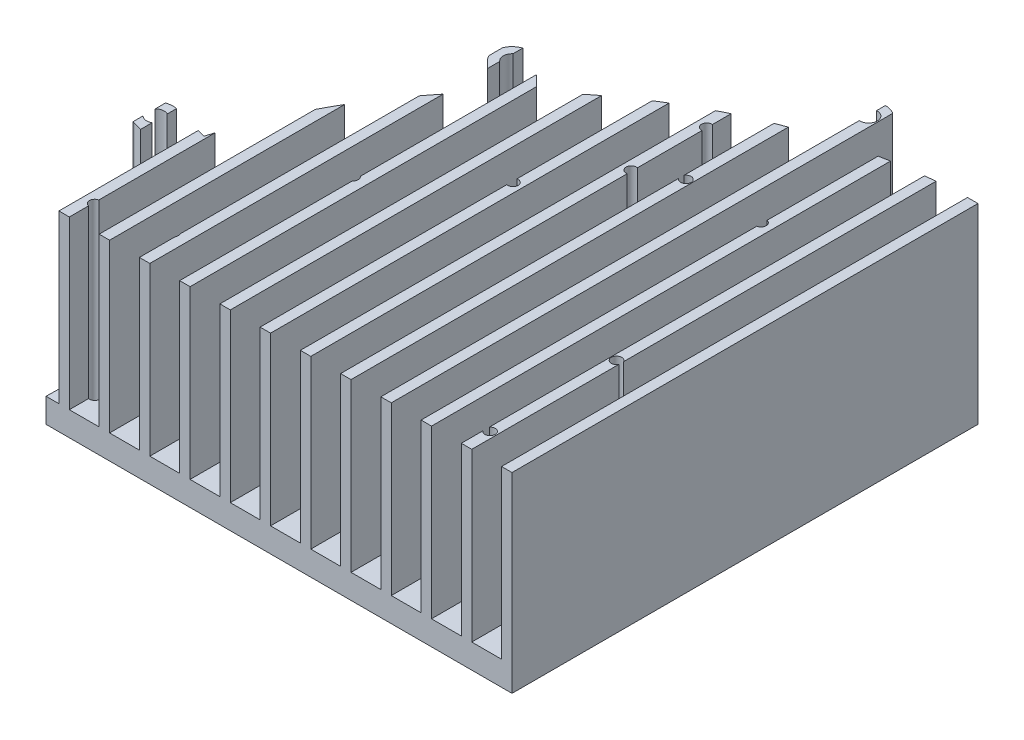
SolidWorks part; units mm, degrees
note: The reader was unsure of these and kept them because the rebuilt part matched: shared geometry of "Sketch3<6>".
ref_plane "Ön Düzlem" through (0, 0, 0) normal (0, 0, 1) x (1, 0, 0)
ref_plane "Üst Düzlem" through (0, 0, 0) normal (0, 1, 0) x (1, 0, 0)
ref_plane "Sağ Düzlem" through (0, 0, 0) normal (1, 0, 0) x (0, 0, -1)
sketch "Sketch1" plane through (0, 0, 0) normal (0, 0, 1) x (1, 0, 0)
  line L0 (11.5714, 7) -> (11.5714, 55)
  line L1 (0, 0) -> (165, 0)
  line L2 (0, 0) -> (0, 7)
  line L3 (3, 7) -> (11.5714, 7)
  line L4 (165, 0) -> (165, 10)
  line L6 (0, 7) -> (0, 55)
  line L7 (0, 55) -> (3, 55)
  line L8 (3, 7) -> (3, 55)
  line L10 (14.5714, 7) -> (14.5714, 55)
  line L11 (11.5714, 55) -> (14.5714, 55)
  line L12 (23.1429, 7) -> (23.1429, 55)
  line L14 (26.1429, 7) -> (26.1429, 55)
  line L15 (23.1429, 55) -> (26.1429, 55)
  line L16 (34.7143, 7) -> (34.7143, 55)
  line L18 (37.7143, 7) -> (37.7143, 55)
  line L19 (34.7143, 55) -> (37.7143, 55)
  line L20 (46.2857, 7) -> (46.2857, 55)
  line L22 (49.2857, 7) -> (49.2857, 55)
  line L23 (46.2857, 55) -> (49.2857, 55)
  line L24 (57.8571, 7) -> (57.8571, 55)
  line L26 (60.8571, 7) -> (60.8571, 55)
  line L27 (57.8571, 55) -> (60.8571, 55)
  line L28 (69.4286, 7) -> (69.4286, 55)
  line L30 (72.4286, 7) -> (72.4286, 55)
  line L31 (69.4286, 55) -> (72.4286, 55)
  line L32 (81, 7) -> (81, 55)
  line L34 (84, 7) -> (84, 55)
  line L35 (81, 55) -> (84, 55)
  line L36 (92.5714, 7) -> (92.5714, 55)
  line L38 (95.5714, 7) -> (95.5714, 55)
  line L39 (92.5714, 55) -> (95.5714, 55)
  line L40 (104.1429, 7) -> (104.1429, 55)
  line L42 (107.1429, 7) -> (107.1429, 55)
  line L43 (104.1429, 55) -> (107.1429, 55)
  line L44 (115.7143, 7) -> (115.7143, 55)
  line L46 (118.7143, 7) -> (118.7143, 55)
  line L47 (115.7143, 55) -> (118.7143, 55)
  line L48 (127.2857, 7) -> (127.2857, 55)
  line L50 (130.2857, 7) -> (130.2857, 55)
  line L51 (127.2857, 55) -> (130.2857, 55)
  line L52 (138.8571, 7) -> (138.8571, 55)
  line L54 (141.8571, 7) -> (141.8571, 55)
  line L55 (138.8571, 55) -> (141.8571, 55)
  line L56 (150.4286, 7) -> (150.4286, 55)
  line L58 (153.4286, 7) -> (153.4286, 55)
  line L59 (150.4286, 55) -> (153.4286, 55)
  line L60 (162, 7) -> (162, 55)
  line L62 (165, 7) -> (165, 55)
  line L63 (162, 55) -> (165, 55)
  line L78 (14.5714, 7) -> (23.1429, 7)
  line L79 (26.1429, 7) -> (34.7143, 7)
  line L80 (37.7143, 7) -> (46.2857, 7)
  line L81 (49.2857, 7) -> (57.8571, 7)
  line L82 (60.8571, 7) -> (69.4286, 7)
  line L83 (72.4286, 7) -> (81, 7)
  line L84 (84, 7) -> (92.5714, 7)
  line L85 (95.5714, 7) -> (104.1429, 7)
  line L86 (107.1429, 7) -> (115.7143, 7)
  line L87 (118.7143, 7) -> (127.2857, 7)
  line L88 (130.2857, 7) -> (138.8571, 7)
  line L89 (141.8571, 7) -> (150.4286, 7)
  line L90 (153.4286, 7) -> (162, 7)
  dimension "D1" = 165
  dimension "D2" = 7
  dimension "D3" = 48
  dimension "D4" = 3
  dimension "D5" = 15
extrude "Boss-Extrude1" add sketch "Sketch1" along normal blind 1000 contours L90 L58 L59 L56 L89 L54 L55 L52 L88 L50 L51 L48 L87 L46 L47 L44 L86 L42 L43 L40 L85 L38 L39 L36 L84 L34 L35 L32 L83 L30 L31 L28 L82 L26 L27 L24 L81 L22 L23 L20 L80 L18 L19 L16 L79 L14 L15 L12 L78 L10 L11
sketch "Sketch3" plane through (0, 0, 0) normal (0, -1, 0) x (1, 0, 0)
  line L1 (165, 1000) -> (165, 0) construction
  line L3 (0, 0) -> (165, 0) construction
  line L23 (165, 200) -> (0, 200) construction
  line L24 (0, 1000) -> (0, 0) construction
  line L25 (165, 334) -> (0, 334) construction
  line L26 (165, 334) -> (118.1105, 159.006) construction
  line L27 (165, 334) -> (36.8955, 205.8955) construction
  line L28 (165, 334) -> (-9.994, 287.1105) construction
  line L29 (165, 334) -> (118.1105, 159.006) construction
  line L30 (165, 334) -> (127.4712, 193.9408) construction
  line L31 (165, 334) -> (127.4712, 193.9408) construction
  line L32 (132.3009, 192.6467) -> (135.172, 203.362)
  line L33 (122.6416, 195.2349) -> (125.5128, 205.9502)
  line L34 (66.0051, 227.934) -> (73.8492, 235.7781)
  line L35 (58.934, 235.0051) -> (66.7781, 242.8492)
  line L36 (26.2349, 291.6416) -> (36.9502, 294.5128)
  line L37 (23.6467, 301.3009) -> (34.362, 304.172)
  line L38 (165, 334) -> (135.172, 203.362) construction
  line L39 (165, 200) -> (165, 334)
  line L40 (165, 334) -> (31, 334)
  line L41 (165, 184) -> (0, 184) construction
  line L42 (165, 344) -> (0, 344) construction
  line L43 (0, 184) -> (0, 344) construction
  line L44 (165, 200) -> (165, 184) construction
  line L45 (165, 344) -> (165, 334) construction
  arc A1 (165, 200) -> (31, 334) centre (165, 334) cw construction
  circle A7 centre (117, 236) radius 1.5
  circle A8 centre (106.834, 241.544) radius 1.5
  arc A10 (165, 184) -> (15, 334) centre (165, 334) cw construction
  arc A11 (165, 189) -> (20, 334) centre (165, 334) cw construction
  circle A12 centre (127.4712, 193.9408) radius 2.5
  circle A13 centre (62.4695, 231.4695) radius 2.5
  circle A14 centre (24.9408, 296.4712) radius 2.5
  arc A15 (122.6646, 195.3179) -> (132.3225, 192.7301) centre (127.4712, 193.9408) ccw
  arc A16 (58.9955, 235.0655) -> (66.0655, 227.9955) centre (62.4695, 231.4695) ccw
  arc A17 (23.7301, 301.3225) -> (26.3179, 291.6646) centre (24.9408, 296.4712) ccw
  arc A18 (165, 200) -> (135.172, 203.362) centre (165, 334) cw
  arc A19 (125.5128, 205.9502) -> (73.8492, 235.7781) centre (165, 334) cw
  arc A20 (66.7781, 242.8492) -> (36.9502, 294.5128) centre (165, 334) cw
  arc A21 (34.362, 304.172) -> (31, 334) centre (165, 334) cw
  circle A22 centre (159, 206) radius 1.5
  circle A23 centre (159.945, 224.958) radius 1.5
  circle A24 centre (138.59, 236) radius 1.5
  circle A25 centre (107, 220) radius 1.5
  circle A26 centre (92.864, 261.61) radius 1.5
  circle A27 centre (74.576, 273.548) radius 1.5
  circle A28 centre (68.48, 283.2) radius 1.5
  circle A29 centre (51, 276) radius 1.5
  circle A30 centre (152.097, 291.028) radius 1.5
  circle A31 centre (133.3, 304.5) radius 1.5
  circle A32 centre (66.702, 306.822) radius 1.5
  circle A33 centre (56.542, 323.078) radius 1.5
  circle A34 centre (38, 327) radius 1.5
  circle A35 centre (124, 325) radius 1.5
  circle A36 centre (158, 321) radius 1.501
  circle A37 centre (151.6, 326.9) radius 1.5
  dimension "D5" = 48
  dimension "D7" = 3
  dimension "D8" = 3
  dimension "D10" = 92.456
  dimension "D20" = 150
  dimension "D21" = 145
  dimension "D22" = 134
  dimension "D23" = 5
  dimension "D26" = 10
  dimension "D32" = 3
  dimension "D35" = 3
  dimension "D38" = 3
  dimension "D41" = 3
  dimension "D11" = 3
  dimension "D44" = 3
  dimension "D47" = 3
  dimension "D50" = 3
  dimension "D53" = 3
  dimension "D56" = 3
  dimension "D61" = 3
  dimension "D62" = 3
  dimension "D65" = 3
  dimension "D68" = 3
  dimension "D69" = 3.002
  dimension "D70" = 3
  dimension "D6" = 98
  dimension "D9" = 58.166
  dimension "D14" = 134
  dimension "D15" = 200
  dimension "D16" = 15
  dimension "D18" = 30
  dimension "D19" = 30
  dimension "D25" = 145
  dimension "D28" = 145
  dimension "D30" = 134
  dimension "D31" = 10
  dimension "D33" = 6
  dimension "D34" = 128
  dimension "D36" = 5.055
  dimension "D37" = 109.042
  dimension "D39" = 26.41
  dimension "D40" = 98
  dimension "D42" = 58
  dimension "D43" = 114
  dimension "D12" = 72.136
  dimension "D13" = 72.39
  dimension "D45" = 60.452
  dimension "D46" = 90.424
  dimension "D48" = 50.8
  dimension "D49" = 96.52
  dimension "D51" = 114
  dimension "D52" = 58
  dimension "D54" = 12.903
  dimension "D55" = 42.972
  dimension "D57" = 29.5
  dimension "D58" = 31.7
  dimension "D59" = 98.298
  dimension "D60" = 27.178
  dimension "D63" = 108.458
  dimension "D64" = 10.922
  dimension "D66" = 7
  dimension "D67" = 127
  dimension "D71" = 41
  dimension "D72" = 9
  dimension "D73" = 7
  dimension "D74" = 13
  dimension "D75" = 13.4
  dimension "D76" = 7.1
  dimension "D17" = 3
  dimension "D24" = 3
  dimension "D27" = 3
  dimension "D29" = 3
extrude "Cut-Extrude3" cut sketch "Sketch3" against normal blind 100
extrude "Cut-Extrude4" cut sketch "Sketch3<6>" against normal blind 100 contours A12 | A13 | A14 | A23 | A22 | A24 | A25 | A7 | A8 | A26 | A27 | A29 | A28 | A32 | A34 | A33 | A35 | A31 | A30 | A37 | A36
sketch "Sketch3<6>" plane through (0, 0, 0) normal (0, -1, 0) x (1, 0, 0) same geometry as "Sketch3"
